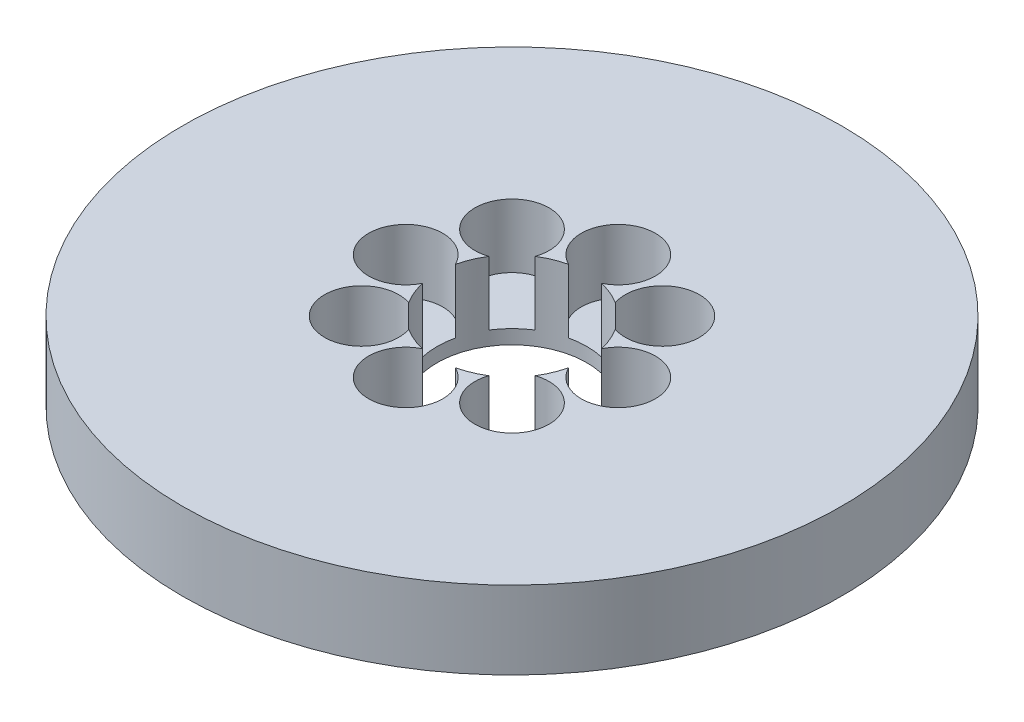
SolidWorks part; units mm, degrees
ref_plane "Front Plane" through (0, 0, 0) normal (0, 0, 1) x (1, 0, 0)
ref_plane "Top Plane" through (0, 0, 0) normal (0, 1, 0) x (1, 0, 0)
ref_plane "Right Plane" through (0, 0, 0) normal (1, 0, 0) x (0, 0, -1)
sketch "Sketch1" plane through (0, 0, 0) normal (0, 1, 0) x (1, 0, 0)
  circle A0 centre (0, 0) radius 55
  dimension "FLANGE_OD" = 110
extrude "Boss-Extrude1" add sketch "Sketch1" along normal blind 13
sketch "Sketch2" plane through (0, 0, 0) normal (0, 1, 0) x (1, 0, 0)
  circle A0 centre (0, 0) radius 12.5
  dimension "BORE_D" = 25
extrude "Cut-Extrude1" cut sketch "Sketch2" along normal through all
sketch "Sketch3" plane through (0, 13, 0) normal (0, 1, 0) x (1, 0, 0)
  circle A0 centre (0, 0) radius 17.7437 construction
  circle A1 centre (-17.7437, 0) radius 6.1876
  dimension "BOLT_D" = 12.3751
  dimension "BOLT_PCD" = 35.4873
extrude "Cut-Extrude2" cut sketch "Sketch3" against normal blind 10.6482
pattern_circular "CirPattern1" count 8 over 360 about axis through (0, 0, 0) along (0, 1, 0) of "Cut-Extrude2"
